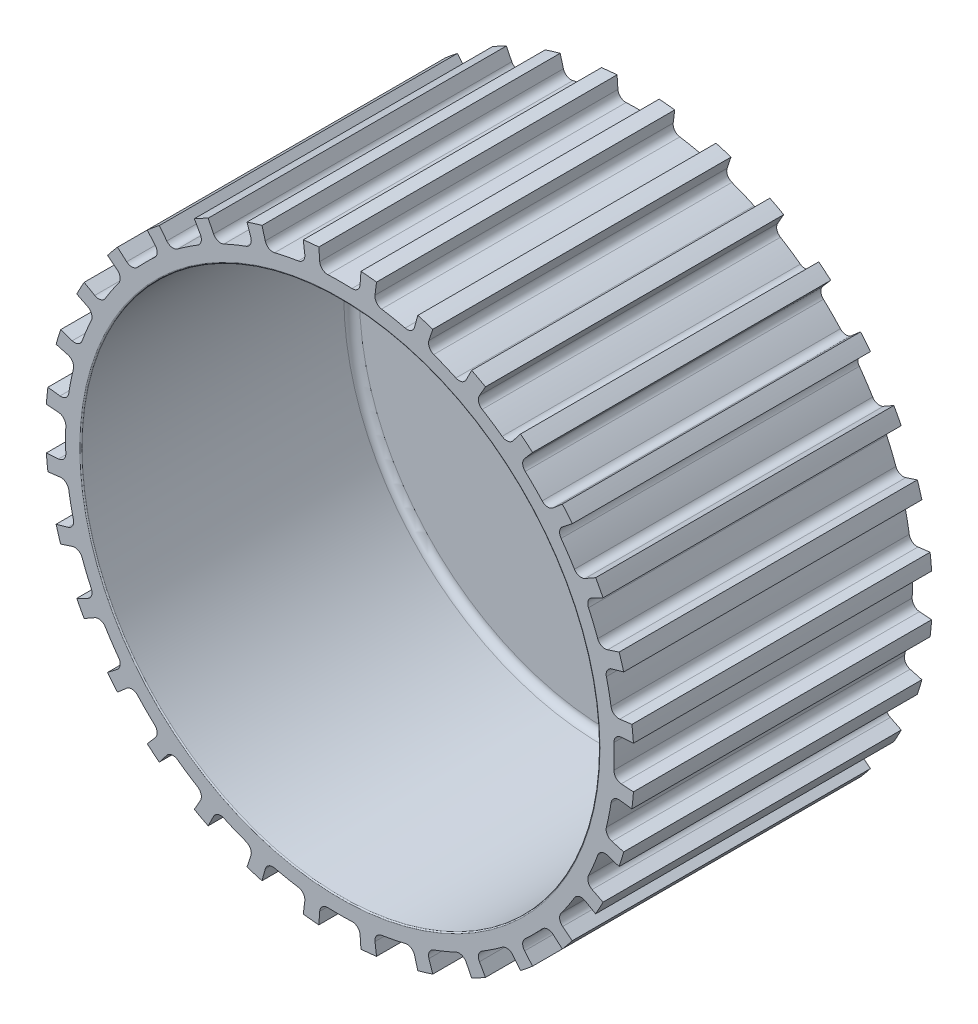
SolidWorks part; units mm, degrees
ref_plane "前视基准面" through (0, 0, 0) normal (0, 0, 1) x (1, 0, 0)
ref_plane "上视基准面" through (0, 0, 0) normal (0, 1, 0) x (1, 0, 0)
ref_plane "右视基准面" through (0, 0, 0) normal (1, 0, 0) x (0, 0, -1)
sketch "草图1" plane through (0, 0, 0) normal (0, 0, 1) x (1, 0, 0)
  circle A0 centre (0, 0) radius 75
  dimension "D1" = 150
extrude "凸台-拉伸1" add sketch "草图1" along normal blind 7
sketch "草图2" plane through (0, 0, 7) normal (0, 0, 1) x (1, 0, 0)
  circle A0 centre (0, 0) radius 75
  circle A1 centre (0, 0) radius 66
  dimension "D1" = 75
  dimension "D2" = 66
extrude "凸台-拉伸2" add sketch "草图2" along normal blind 69
sketch "草图4" plane through (0, 0, 7) normal (0, 0, 1) x (1, 0, 0)
  circle A0 centre (0, 0) radius 14
  dimension "D1" = 14
extrude "凸台-拉伸3" add sketch "草图4" along normal blind 7
sketch "草图5" plane through (0, 0, 0) normal (0, 0, -1) x (-1, 0, 0)
  line L0 (0, 14) -> (0, -14) construction
  line L1 (14, 0) -> (-14, 0) construction
  circle A0 centre (0, 0) radius 14 construction
  circle A1 centre (0, 0) radius 14 construction
  circle A2 centre (0, 0) radius 5.05
  circle A3 centre (0, 8) radius 1.2
  circle A4 centre (8, 0) radius 1.2
  circle A5 centre (0, -8) radius 1.2
  circle A6 centre (-8, 0) radius 1.2
  point P22 (0, 0)
  dimension "D1" = 5.05
  dimension "D2" = 1.2
  dimension "D3" = 8
  dimension "D4" = 4
extrude "切除-拉伸2" cut sketch "草图5" against normal through all
sketch "草图6" plane through (0, 0, 76) normal (0, 0, 1) x (1, 0, 0)
  line L0 (0, 0) -> (0, 75) construction
  line L5 (0, 0) -> (5, 69.739) construction
  line L6 (0, 0) -> (-5, 69.739) construction
  line L7 (5.6944, 79.4238) -> (5, 69.739)
  line L8 (-5.6944, 79.4238) -> (-5, 69.739)
  line L9 (9.9099, 79.0086) -> (8.7015, 69.3744)
  line L10 (21.0798, 76.7868) -> (18.5093, 67.4235)
  line L11 (25.1333, 75.5572) -> (22.0686, 66.3438)
  line L12 (35.6551, 71.1989) -> (31.3074, 62.517)
  line L13 (39.3908, 69.2021) -> (34.5876, 60.7637)
  line L14 (48.8602, 62.8749) -> (42.9023, 55.208)
  line L15 (52.1346, 60.1876) -> (45.7774, 52.8485)
  line L16 (60.1876, 52.1346) -> (52.8485, 45.7774)
  line L17 (62.8749, 48.8602) -> (55.208, 42.9023)
  line L18 (69.2021, 39.3908) -> (60.7637, 34.5876)
  line L19 (71.1989, 35.6551) -> (62.517, 31.3074)
  line L20 (75.5572, 25.1333) -> (66.3438, 22.0686)
  line L21 (76.7868, 21.0798) -> (67.4235, 18.5093)
  line L22 (79.0086, 9.9099) -> (69.3744, 8.7015)
  line L23 (79.4238, 5.6944) -> (69.739, 5)
  line L24 (79.4238, -5.6944) -> (69.739, -5)
  line L25 (79.0086, -9.9099) -> (69.3744, -8.7015)
  line L26 (76.7868, -21.0798) -> (67.4235, -18.5093)
  line L27 (75.5572, -25.1333) -> (66.3438, -22.0686)
  line L28 (71.1989, -35.6551) -> (62.517, -31.3074)
  line L29 (69.2021, -39.3908) -> (60.7637, -34.5876)
  line L30 (62.8749, -48.8602) -> (55.208, -42.9023)
  line L31 (60.1876, -52.1346) -> (52.8485, -45.7774)
  line L32 (52.1346, -60.1876) -> (45.7774, -52.8485)
  line L33 (48.8602, -62.8749) -> (42.9023, -55.208)
  line L34 (39.3908, -69.2021) -> (34.5876, -60.7637)
  line L35 (35.6551, -71.1989) -> (31.3074, -62.517)
  line L36 (25.1333, -75.5572) -> (22.0686, -66.3438)
  line L37 (21.0798, -76.7868) -> (18.5093, -67.4235)
  line L38 (9.9099, -79.0086) -> (8.7015, -69.3744)
  line L39 (5.6944, -79.4238) -> (5, -69.739)
  line L40 (-5.6944, -79.4238) -> (-5, -69.739)
  line L41 (-9.9099, -79.0086) -> (-8.7015, -69.3744)
  line L42 (-21.0798, -76.7868) -> (-18.5093, -67.4235)
  line L43 (-25.1333, -75.5572) -> (-22.0686, -66.3438)
  line L44 (-35.6551, -71.1989) -> (-31.3074, -62.517)
  line L45 (-39.3908, -69.2021) -> (-34.5876, -60.7637)
  line L46 (-48.8602, -62.8749) -> (-42.9023, -55.208)
  line L47 (-52.1346, -60.1876) -> (-45.7774, -52.8485)
  line L48 (-60.1876, -52.1346) -> (-52.8485, -45.7774)
  line L49 (-62.8749, -48.8602) -> (-55.208, -42.9023)
  line L50 (-69.2021, -39.3908) -> (-60.7637, -34.5876)
  line L51 (-71.1989, -35.6551) -> (-62.517, -31.3074)
  line L52 (-75.5572, -25.1333) -> (-66.3438, -22.0686)
  line L53 (-76.7868, -21.0798) -> (-67.4235, -18.5093)
  line L54 (-79.0086, -9.9099) -> (-69.3744, -8.7015)
  line L55 (-79.4238, -5.6944) -> (-69.739, -5)
  line L56 (-79.4238, 5.6944) -> (-69.739, 5)
  line L57 (-79.0086, 9.9099) -> (-69.3744, 8.7015)
  line L58 (-76.7868, 21.0798) -> (-67.4235, 18.5093)
  line L59 (-75.5572, 25.1333) -> (-66.3438, 22.0686)
  line L60 (-71.1989, 35.6551) -> (-62.517, 31.3074)
  line L61 (-69.2021, 39.3908) -> (-60.7637, 34.5876)
  line L62 (-62.8749, 48.8602) -> (-55.208, 42.9023)
  line L63 (-60.1876, 52.1346) -> (-52.8485, 45.7774)
  line L64 (-52.1346, 60.1876) -> (-45.7774, 52.8485)
  line L65 (-48.8602, 62.8749) -> (-42.9023, 55.208)
  line L66 (-39.3908, 69.2021) -> (-34.5876, 60.7637)
  line L67 (-35.6551, 71.1989) -> (-31.3074, 62.517)
  line L68 (-25.1333, 75.5572) -> (-22.0686, 66.3438)
  line L69 (-21.0798, 76.7868) -> (-18.5093, 67.4235)
  line L70 (-9.9099, 79.0086) -> (-8.7015, 69.3744)
  circle A0 centre (0, 0) radius 70 construction
  arc A1 (-5, 69.739) -> (5, 69.739) centre (0, 0) cw
  arc A2 (-5.6944, 79.4238) -> (5.6944, 79.4238) centre (0, 0) cw
  arc A3 (9.9099, 79.0086) -> (21.0798, 76.7868) centre (0, 0) cw
  arc A4 (8.7015, 69.3744) -> (18.5093, 67.4235) centre (0, 0) cw
  arc A5 (25.1333, 75.5572) -> (35.6551, 71.1989) centre (0, 0) cw
  arc A6 (22.0686, 66.3438) -> (31.3074, 62.517) centre (0, 0) cw
  arc A7 (39.3908, 69.2021) -> (48.8602, 62.8749) centre (0, 0) cw
  arc A8 (34.5876, 60.7637) -> (42.9023, 55.208) centre (0, 0) cw
  arc A9 (52.1346, 60.1876) -> (60.1876, 52.1346) centre (0, 0) cw
  arc A10 (45.7774, 52.8485) -> (52.8485, 45.7774) centre (0, 0) cw
  arc A11 (62.8749, 48.8602) -> (69.2021, 39.3908) centre (0, 0) cw
  arc A12 (55.208, 42.9023) -> (60.7637, 34.5876) centre (0, 0) cw
  arc A13 (71.1989, 35.6551) -> (75.5572, 25.1333) centre (0, 0) cw
  arc A14 (62.517, 31.3074) -> (66.3438, 22.0686) centre (0, 0) cw
  arc A15 (76.7868, 21.0798) -> (79.0086, 9.9099) centre (0, 0) cw
  arc A16 (67.4235, 18.5093) -> (69.3744, 8.7015) centre (0, 0) cw
  arc A17 (79.4238, 5.6944) -> (79.4238, -5.6944) centre (0, 0) cw
  arc A18 (69.739, 5) -> (69.739, -5) centre (0, 0) cw
  arc A19 (79.0086, -9.9099) -> (76.7868, -21.0798) centre (0, 0) cw
  arc A20 (69.3744, -8.7015) -> (67.4235, -18.5093) centre (0, 0) cw
  arc A21 (75.5572, -25.1333) -> (71.1989, -35.6551) centre (0, 0) cw
  arc A22 (66.3438, -22.0686) -> (62.517, -31.3074) centre (0, 0) cw
  arc A23 (69.2021, -39.3908) -> (62.8749, -48.8602) centre (0, 0) cw
  arc A24 (60.7637, -34.5876) -> (55.208, -42.9023) centre (0, 0) cw
  arc A25 (60.1876, -52.1346) -> (52.1346, -60.1876) centre (0, 0) cw
  arc A26 (52.8485, -45.7774) -> (45.7774, -52.8485) centre (0, 0) cw
  arc A27 (48.8602, -62.8749) -> (39.3908, -69.2021) centre (0, 0) cw
  arc A28 (42.9023, -55.208) -> (34.5876, -60.7637) centre (0, 0) cw
  arc A29 (35.6551, -71.1989) -> (25.1333, -75.5572) centre (0, 0) cw
  arc A30 (31.3074, -62.517) -> (22.0686, -66.3438) centre (0, 0) cw
  arc A31 (21.0798, -76.7868) -> (9.9099, -79.0086) centre (0, 0) cw
  arc A32 (18.5093, -67.4235) -> (8.7015, -69.3744) centre (0, 0) cw
  arc A33 (5.6944, -79.4238) -> (-5.6944, -79.4238) centre (0, 0) cw
  arc A34 (5, -69.739) -> (-5, -69.739) centre (0, 0) cw
  arc A35 (-9.9099, -79.0086) -> (-21.0798, -76.7868) centre (0, 0) cw
  arc A36 (-8.7015, -69.3744) -> (-18.5093, -67.4235) centre (0, 0) cw
  arc A37 (-25.1333, -75.5572) -> (-35.6551, -71.1989) centre (0, 0) cw
  arc A38 (-22.0686, -66.3438) -> (-31.3074, -62.517) centre (0, 0) cw
  arc A39 (-39.3908, -69.2021) -> (-48.8602, -62.8749) centre (0, 0) cw
  arc A40 (-34.5876, -60.7637) -> (-42.9023, -55.208) centre (0, 0) cw
  arc A41 (-52.1346, -60.1876) -> (-60.1876, -52.1346) centre (0, 0) cw
  arc A42 (-45.7774, -52.8485) -> (-52.8485, -45.7774) centre (0, 0) cw
  arc A43 (-62.8749, -48.8602) -> (-69.2021, -39.3908) centre (0, 0) cw
  arc A44 (-55.208, -42.9023) -> (-60.7637, -34.5876) centre (0, 0) cw
  arc A45 (-71.1989, -35.6551) -> (-75.5572, -25.1333) centre (0, 0) cw
  arc A46 (-62.517, -31.3074) -> (-66.3438, -22.0686) centre (0, 0) cw
  arc A47 (-76.7868, -21.0798) -> (-79.0086, -9.9099) centre (0, 0) cw
  arc A48 (-67.4235, -18.5093) -> (-69.3744, -8.7015) centre (0, 0) cw
  arc A49 (-79.4238, -5.6944) -> (-79.4238, 5.6944) centre (0, 0) cw
  arc A50 (-69.739, -5) -> (-69.739, 5) centre (0, 0) cw
  arc A51 (-79.0086, 9.9099) -> (-76.7868, 21.0798) centre (0, 0) cw
  arc A52 (-69.3744, 8.7015) -> (-67.4235, 18.5093) centre (0, 0) cw
  arc A53 (-75.5572, 25.1333) -> (-71.1989, 35.6551) centre (0, 0) cw
  arc A54 (-66.3438, 22.0686) -> (-62.517, 31.3074) centre (0, 0) cw
  arc A55 (-69.2021, 39.3908) -> (-62.8749, 48.8602) centre (0, 0) cw
  arc A56 (-60.7637, 34.5876) -> (-55.208, 42.9023) centre (0, 0) cw
  arc A57 (-60.1876, 52.1346) -> (-52.1346, 60.1876) centre (0, 0) cw
  arc A58 (-52.8485, 45.7774) -> (-45.7774, 52.8485) centre (0, 0) cw
  arc A59 (-48.8602, 62.8749) -> (-39.3908, 69.2021) centre (0, 0) cw
  arc A60 (-42.9023, 55.208) -> (-34.5876, 60.7637) centre (0, 0) cw
  arc A61 (-35.6551, 71.1989) -> (-25.1333, 75.5572) centre (0, 0) cw
  arc A62 (-31.3074, 62.517) -> (-22.0686, 66.3438) centre (0, 0) cw
  arc A63 (-21.0798, 76.7868) -> (-9.9099, 79.0086) centre (0, 0) cw
  arc A64 (-18.5093, 67.4235) -> (-8.7015, 69.3744) centre (0, 0) cw
  point P13 (0, 84.9238)
  point P142 (0, 0)
  dimension "D1" = 70
  dimension "D2" = 32
extrude "切除-拉伸3" cut sketch "草图6" against normal through all
fillet "圆角2" radius 2 64 edges at (8.7015, 69.3744, 38) (22.0686, 66.3438, 38) (34.5876, 60.7637, 38) (45.7774, 52.8485, 38) (55.208, 42.9023, 38) (62.517, 31.3074, 38) (67.4235, 18.5093, 38) (69.739, 5, 38) (69.3744, -8.7015, 38) (66.3438, -22.0686, 38) (52.8485, -45.7774, 38) (31.3074, -62.517, 38) (18.5093, -67.4235, 38) (5, -69.739, 38) (-8.7015, -69.3744, 38) (-22.0686, -66.3438, 38) (-34.5876, -60.7637, 38) (-45.7774, -52.8485, 38) (-55.208, -42.9023, 38) (-62.517, -31.3074, 38) (-67.4235, -18.5093, 38) (-69.739, -5, 38) (-69.3744, 8.7015, 38) (-66.3438, 22.0686, 38) (-60.7637, 34.5876, 38) (-52.8485, 45.7774, 38) (-42.9023, 55.208, 38) (-31.3074, 62.517, 38) (-18.5093, 67.4235, 38) (-22.0686, 66.3438, 38) (-34.5876, 60.7637, 38) (-45.7774, 52.8485, 38) (-55.208, 42.9023, 38) (-62.517, 31.3074, 38) (-67.4235, 18.5093, 38) (-69.739, 5, 38) (-69.3744, -8.7015, 38) (-66.3438, -22.0686, 38) (-60.7637, -34.5876, 38) (-52.8485, -45.7774, 38) (-42.9023, -55.208, 38) (-31.3074, -62.517, 38) (-18.5093, -67.4235, 38) (-5, -69.739, 38) (8.7015, -69.3744, 38) (22.0686, -66.3438, 38) (34.5876, -60.7637, 38) (45.7774, -52.8485, 38) (55.208, -42.9023, 38) (62.517, -31.3074, 38) (67.4235, -18.5093, 38) (69.739, -5, 38) (69.3744, 8.7015, 38) (66.3438, 22.0686, 38) (60.7637, 34.5876, 38) (52.8485, 45.7774, 38) (42.9023, 55.208, 38) (31.3074, 62.517, 38) (18.5093, 67.4235, 38) (5, 69.739, 38) (-5, 69.739, 38) (-8.7015, 69.3744, 38) (60.7637, -34.5876, 38) (42.9023, -55.208, 38)
fillet "Fillet1" radius 2 1 edges at (66, 0, 7)
chamfer "Chamfer1" distance 0.3 angle 45 1 edges at (5.05, 0, 14)
fillet "Fillet2" radius 0.3 1 edges at (66, 0, 76)
sketch "草图8" plane through (0, 0, 14) normal (0, 0, 1) x (1, 0, 0)
  line L0 (0, 14) -> (0, -14) construction
  line L1 (-14, 0) -> (14, 0) construction
  line L2 (0, 0) -> (-9.8995, 9.8995) construction
  circle A0 centre (0, 0) radius 14 construction
  circle A1 centre (0, 0) radius 14 construction
  circle A3 centre (-7.7782, 7.7782) radius 1.45
  circle A4 centre (7.7782, 7.7782) radius 1.45
  circle A5 centre (7.7782, -7.7782) radius 1.45
  circle A6 centre (-7.7782, -7.7782) radius 1.45
  point P31 (0, 0)
  dimension "D1" = 45
  dimension "D2" = 2.9
  dimension "D3" = 11
  dimension "D4" = 4
fillet "圆角3" radius 8 1 edges at (14, 0, 7)
extrude "切除-拉伸5" cut sketch "草图8" against normal through all
